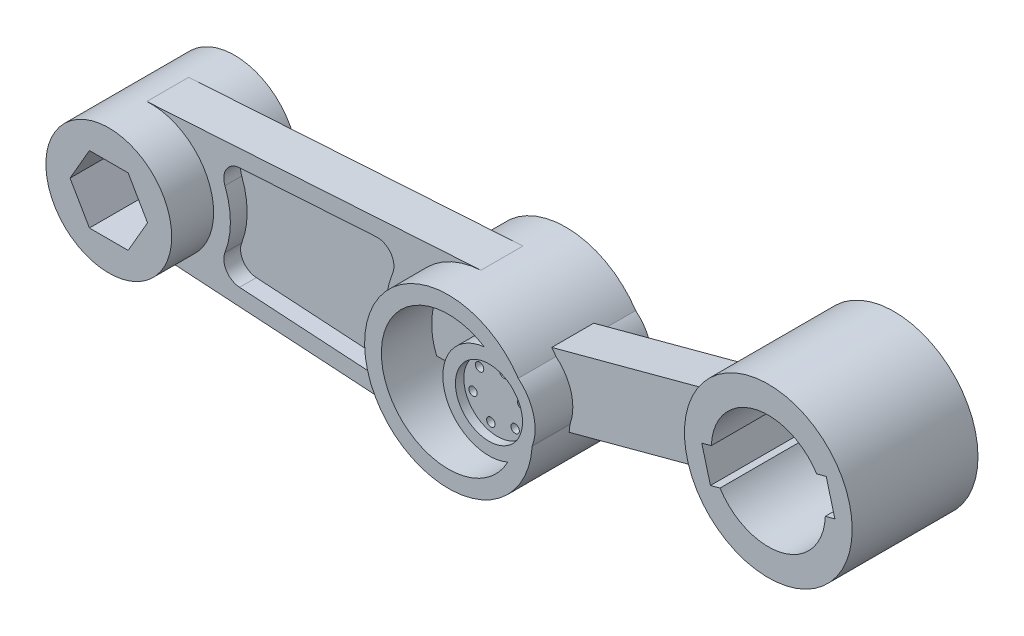
SolidWorks part; units mm, degrees
material "Copper"
ref_plane "Front Plane" through (0, 0, 0) normal (0, 0, 1) x (1, 0, 0)
ref_plane "Top Plane" through (0, 0, 0) normal (0, 1, 0) x (1, 0, 0)
ref_plane "Right Plane" through (0, 0, 0) normal (1, 0, 0) x (0, 0, -1)
ref_plane "CENTRE_Plane" through (200, 0, 0) normal (1, 0, 0) x (0, 0, -1)
ref_axis "CENTRE_Plane_Axis" through (200, 0, 38.5) along (0, 0, -1)
ref_plane "CENTRE_RIGHT_Plane" through (186.6025, 50, 0) normal (0.9659, 0.2588, 0) x (0, 0, -1)
ref_plane "RIGHT_Plane" through (379.7877, 101.7638, 0) normal (0.9659, 0.2588, 0) x (0, 0, -1)
sketch "Sketch1" plane through (0, 0, 0) normal (0, 0, 1) x (1, 0, 0)
  line L0 (-2.3437, 37.4267) -> (196.875, 49.9022)
  line L1 (-2.3437, -37.4267) -> (196.875, -49.9022)
  arc A0 (-2.3437, 37.4267) -> (-2.3437, -37.4267) centre (0, 0) ccw
  arc A1 (196.875, -49.9022) -> (196.875, 49.9022) centre (200, 0) ccw
  dimension "D1" = 75
  dimension "D2" = 100
extrude "LEFT_ARM" add sketch "Sketch1" along normal mid plane 25
sketch "Sketch2" plane through (0, 0, 0) normal (0, 0, 1) x (1, 0, 0)
  circle A0 centre (0, 0) radius 37.5
  dimension "D1" = 75
extrude "LEFT_Boss" add sketch "Sketch2" along normal mid plane 75
sketch "Sketch4" plane through (0, 0, 37.5) normal (0, 0, 1) x (1, 0, 0)
  line L0 (38.5, 0) -> (-38.5, 0) construction
  line L1 (23.094, 0) -> (11.547, 20)
  line L2 (11.547, 20) -> (-11.547, 20)
  line L3 (-11.547, 20) -> (-23.094, 0)
  line L4 (-23.094, 0) -> (-11.547, -20)
  line L5 (-11.547, -20) -> (11.547, -20)
  line L6 (11.547, -20) -> (23.094, 0)
  circle A0 centre (0, 0) radius 20 construction
  dimension "D1" = 40
extrude "LEFT_Hex" cut sketch "Sketch4" against normal through all both and the other way through all
sketch "Sketch3" plane through (0, 0, 0) normal (0, 0, 1) x (1, 0, 0)
  circle A0 centre (200, 0) radius 50
  dimension "D1" = 100
extrude "CENTRE_Boss" add sketch "Sketch3" along normal mid plane 70
sketch "Sketch5" plane through (186.6025, 50, 0) normal (0.9659, 0.2588, 0) x (0, 0, -1)
  line L0 (-38.5, -51.7638) -> (38.5, -51.7638) construction
  line L1 (-12.5, -71.7638) -> (12.5, -71.7638)
  line L2 (-12.5, -71.7638) -> (-12.5, -31.7638)
  line L3 (-12.5, -31.7638) -> (12.5, -31.7638)
  line L4 (12.5, -71.7638) -> (12.5, -31.7638)
  line L5 (-12.5, -71.7638) -> (12.5, -31.7638) construction
  line L6 (-12.5, -31.7638) -> (12.5, -71.7638) construction
  line L7 (0, 83.4701) -> (0, -83.4701) construction
  point P0 (0, -51.7638)
  dimension "D1" = 25
  dimension "D2" = 40
extrude "RIGHT_ARM" add sketch "Sketch5" along normal up to surface (200 mm away) up to plane "RIGHT_Plane"
sketch "RIGHT_ARM_CL" plane through (0, 0, 0) normal (0, 0, 1) x (1, 0, 0)
  line L0 (200, 0) -> (393.1852, 51.7638) construction
  line L1 (395.0941, 44.6397) -> (364.4813, 158.888) construction
sketch "Sketch7" plane through (0, 0, 0) normal (0, 0, 1) x (1, 0, 0)
  circle A0 centre (393.1852, 51.7638) radius 50
  dimension "D1" = 100
extrude "RIGHT_Boss" add sketch "Sketch7" along normal mid plane 75
sketch "Sketch8" plane through (0, 0, 37.5) normal (0, 0, 1) x (1, 0, 0)
  circle A0 centre (393.1852, 51.7638) radius 34
  dimension "D1" = 68
extrude "RIGHT_Boss_Hole" cut sketch "Sketch8" against normal through all
sketch "Sketch9" plane through (0, 0, 35) normal (0, 0, 1) x (1, 0, 0)
  circle A0 centre (200, 0) radius 40
  dimension "D1" = 80
extrude "CENTRE_Hole" cut sketch "Sketch9" against normal through all
sketch "Sketch10" plane through (0, 0, 0) normal (0, 0, 1) x (1, 0, 0)
  line L0 (200, 0) -> (393.1852, 51.7638) construction
  line L1 (202.2611, -8.4385) -> (170.944, 108.4385) construction
  circle A0 centre (224.1481, 6.4705) radius 27.5
  dimension "D1" = 55
  dimension "D2" = 25
extrude "CENTRE_Blob" add sketch "Sketch10" along normal mid plane 70
sketch "Sketch11" plane through (200, 0, 0) normal (1, 0, 0) x (0, 0, -1)
  line L1 (-5, -15) -> (5, -15)
  line L2 (-5, -15) -> (-5, 15)
  line L3 (-5, 15) -> (5, 15)
  line L4 (5, -15) -> (5, 15)
  line L5 (-5, -15) -> (5, 15) construction
  line L6 (-5, 15) -> (5, -15) construction
  point P0 (0, 0)
  dimension "D1" = 10
  dimension "D2" = 30
extrude "CENTRE_Beam" add sketch "Sketch11" along normal up to next and the other way up to next
sketch "Sketch12" plane through (0, 0, 35) normal (0, 0, 1) x (1, 0, 0)
  circle A0 centre (224.1481, 6.4705) radius 20
  dimension "D1" = 40
extrude "Cut-Extrude4" cut sketch "Sketch12" against normal blind 5
hole_wizard "M6x1.0 Tapped Hole1" positions "Sketch13" profile "Sketch14" tap size "M6x1.0" standard "ANSI Metric" end condition up to next
sketch "Sketch13" plane through (0, 0, 30) normal (0, 0, 1) x (1, 0, 0)
  line L0 (200, 0) -> (393.1852, 51.7638) construction
  circle A0 centre (224.1481, 6.4705) radius 20 construction
  point P0 (209.6593, 2.5882)
  dimension "D1" = 15
sketch "Sketch14" plane through (209.6593, 2.5882, 30) normal (1, 0, 0) x (0, -1, 0)
  line L0 (0, 0) -> (0, 65)
  line L1 (0, 65) -> (2.5, 65)
  line L2 (2.5, 65) -> (2.5, 0)
  line L5 (2.5, 0) -> (0, 0)
  line L11 (0, -6.35) -> (0, 107.95) construction
  dimension "Thru Tap Drill Dia." = 5
  dimension "Thru Tap Drill Depth" = 65
cosmetic thread "Hole Thread25" parameters "D2"=6
pattern_circular "CirPattern1" count 6 over 360 about axis through (224.1481, 6.4705, 30) along (0, 0, 1) of "M6x1.0 Tapped Hole1"
cosmetic thread "Hole Thread26" parameters "D2"=6
cosmetic thread "Hole Thread27" parameters "D2"=6
cosmetic thread "Hole Thread28" parameters "D2"=6
cosmetic thread "Hole Thread29" parameters "D2"=6
cosmetic thread "Hole Thread30" parameters "D2"=6
cosmetic thread "Hole Thread31" parameters "D2"=6
cosmetic thread "Hole Thread32" parameters "D2"=6
mirror "Mirror1" about plane through (0, 0, 0) normal (0, 0, 1) of "Cut-Extrude4"
sketch "Sketch15" plane through (0, 0, 12.5) normal (0, 0, 1) x (1, 0, 0)
  line L24 (152.8661, 37.1267) -> (-1.7188, 27.4462)
  line L25 (-1.7187, -27.4462) -> (152.8661, -37.1267)
  line L26 (152.8661, 37.1267) -> (36.9354, 29.8669)
  line L27 (36.9354, -29.8669) -> (152.8661, -37.1267)
  arc A12 (152.8661, 37.1267) -> (152.8661, -37.1267) centre (200, 0) ccw
  arc A13 (152.8661, 37.1267) -> (152.8661, -37.1267) centre (200, 0) ccw
  arc A23 (-2.9687, -47.4071) -> (-2.9687, 47.4071) centre (0, 0) ccw
  arc A24 (36.9354, -29.8669) -> (36.9354, 29.8669) centre (0, 0) ccw
  dimension "D1" = 10
  dimension "D2" = 10
extrude "Cut_OUT" cut sketch "Sketch15" against normal blind 10
fillet "Fillet1" radius 10 4 edges at (152.8661, 37.1267, 7.5) (152.8661, -37.1267, 7.5) (36.9354, -29.8669, 7.5) (36.9354, 29.8669, 7.5)
mirror "Mirror2" about plane through (0, 0, 0) normal (0, 0, 1) of "Fillet1", "Cut_OUT"
sketch "Sketch16" plane through (0, 0, 0) normal (0, 0, 1) x (1, 0, 0)
  line L0 (395.7734, 42.1046) -> (390.597, 61.4231)
  line L1 (395.0941, 44.6397) -> (364.4813, 158.888) construction
  line L2 (390.597, 61.4231) -> (353.5054, 51.4844)
  line L3 (353.5054, 51.4844) -> (358.6818, 32.1659)
  line L4 (358.6818, 32.1659) -> (395.7734, 42.1046)
  circle A0 centre (393.1852, 51.7638) radius 34 construction
  point P4 (393.1852, 51.7638)
  dimension "D1" = 20
  dimension "D2" = 38.4
extrude "KEYWAY" cut sketch "Sketch16" against normal through all both and the other way through all
mirror "Mirror3" about plane through (379.7877, 101.7638, 0) normal (0.9659, 0.2588, 0) of "KEYWAY"
equation "\"D1@Sketch2\"=\"D1@Sketch1\""
equation "\"D1@Sketch3\"=\"D2@Sketch1\""
equation "\"D2@Sketch16\"=34+4.4"
